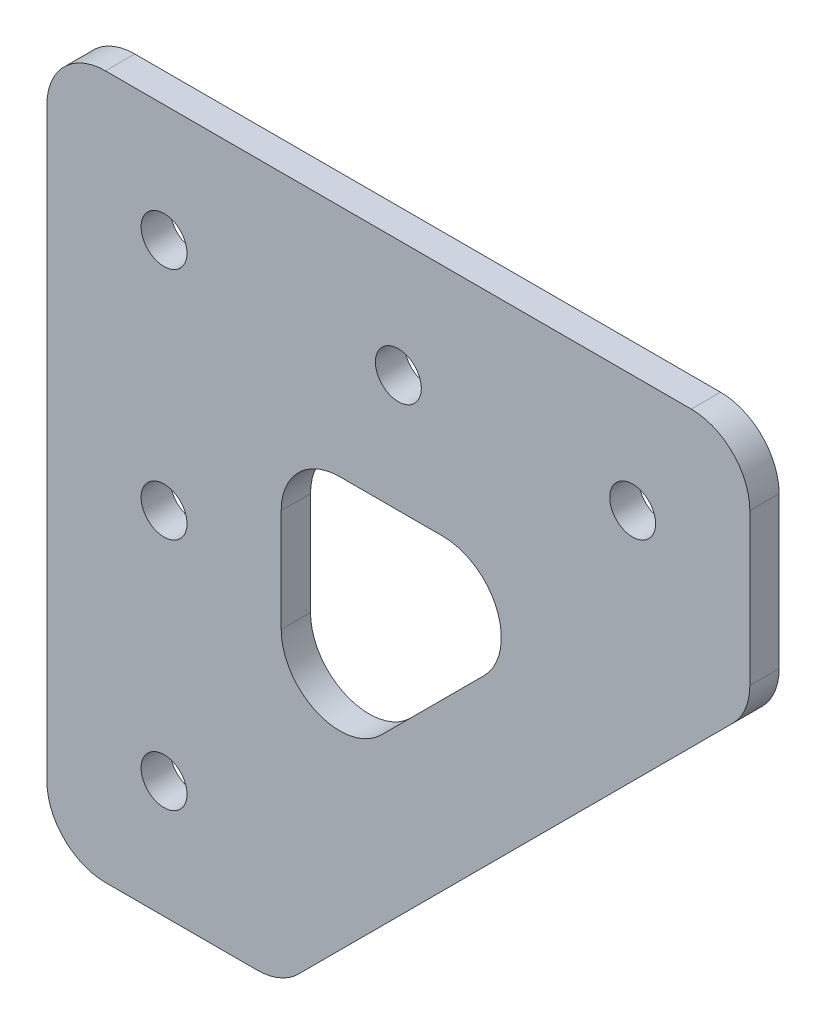
SolidWorks part; units mm, degrees
material "6061-T6 (SS)"
ref_plane "Front Plane" through (0, 0, 0) normal (0, 0, 1) x (1, 0, 0)
ref_plane "Top Plane" through (0, 0, 0) normal (0, 1, 0) x (1, 0, 0)
ref_plane "Right Plane" through (0, 0, 0) normal (1, 0, 0) x (0, 0, -1)
sketch "Sketch1" plane through (0, 0, 0) normal (0, 0, 1) x (1, 0, 0)
  line L0 (0, 0) -> (0, 76.2)
  line L9 (0, 76.2) -> (76.2, 76.2)
  line L10 (76.2, 76.2) -> (76.2, 50.8)
  line L11 (58.2395, 50.8) -> (25.4, 50.8)
  line L12 (25.4, 50.8) -> (25.4, 17.9605)
  line L13 (25.4, 0) -> (0, 0)
  line L14 (25.4, 0) -> (76.2, 50.8)
  line L15 (58.2395, 50.8) -> (25.4, 17.9605)
  dimension "D1" = 25.4
  dimension "D2" = 25.4
  dimension "D3" = 76.2
  dimension "D4" = 76.2
  dimension "D5" = 12.7
extrude "Boss-Extrude1" add sketch "Sketch1" against normal blind 3.175 contours L13 L14 L10 L9 L0 L11 L15 L12 region at (1.0776, 38.1, 0)
sketch "Sketch2" plane through (0, 0, 0) normal (0, 0, 1) x (1, 0, 0)
  line L0 (0, 76.2) -> (76.2, 76.2) construction
  line L1 (0, 0) -> (0, 76.2) construction
  circle A0 centre (12.7, 63.5) radius 2.4892
  circle A1 centre (38.1, 63.5) radius 2.4892
  circle A2 centre (63.5, 63.5) radius 2.4892
  circle A3 centre (12.7, 38.1) radius 2.4892
  circle A4 centre (12.7, 12.7) radius 2.4892
  dimension "D3" = 4.9784
  dimension "D1" = 12.7
  dimension "D2" = 12.7
  dimension "D4" = 3
  dimension "D5" = 3
extrude "Cut-Extrude1" cut sketch "Sketch2" against normal through all
fillet "Fillet3" radius 6.35 8 edges at (58.2395, 50.8, -1.5875) (25.4, 17.9605, -1.5875) (25.4, 50.8, -1.5875) (25.4, 0, -1.5875) (76.2, 50.8, -1.5875) (76.2, 76.2, -1.5875) (0, 0, -1.5875) (0, 76.2, -1.5875)
